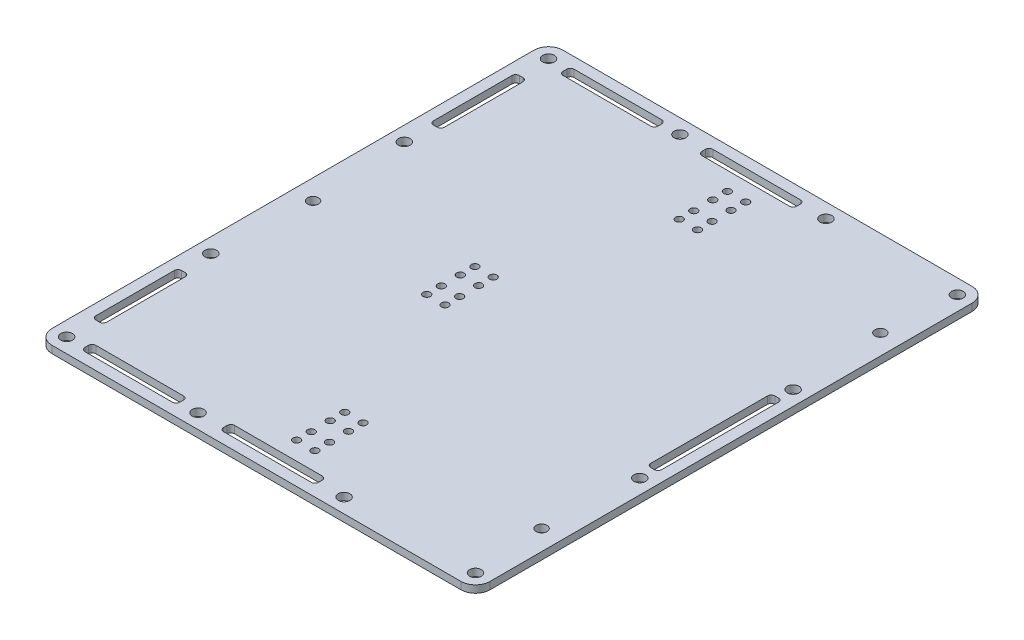
SolidWorks part; units mm, degrees
ref_plane "Front Plane" through (0, 0, 0) normal (0, 0, 1) x (1, 0, 0)
ref_plane "Top Plane" through (0, 0, 0) normal (0, 1, 0) x (1, 0, 0)
ref_plane "Right Plane" through (0, 0, 0) normal (1, 0, 0) x (0, 0, -1)
sketch "Sketch1" plane through (0, 0, 0) normal (0, 1, 0) x (1, 0, 0)
  line L1 (-60, -70) -> (60, -70)
  line L2 (-60, -70) -> (-60, 70)
  line L3 (-60, 70) -> (60, 70)
  line L4 (60, -70) -> (60, 70)
  line L5 (-60, -70) -> (60, 70) construction
  line L6 (-60, 70) -> (60, -70) construction
  point P0 (0, 0)
  dimension "D1" = 120
  dimension "D2" = 140
extrude "Boss-Extrude1" add sketch "Sketch1" along normal blind 4
sketch "Sketch9" plane through (0, 4, 0) normal (0, 1, 0) x (1, 0, 0)
  line L0 (-60, 70) -> (-60, -70) construction
  line L3 (60, -70) -> (60, 70) construction
  line L4 (60, 70) -> (-60, 70) construction
  line L5 (-60, -70) -> (60, -70) construction
  line L7 (-56, -70) -> (56, -70)
  line L8 (-60, -66) -> (-60, 66)
  line L9 (-56, 70) -> (56, 70)
  line L10 (60, -66) -> (60, 66)
  line L11 (-60, -70) -> (60, -70)
  line L12 (-60, -70) -> (-60, 70)
  line L13 (-60, 70) -> (60, 70)
  line L14 (60, -70) -> (60, 70)
  circle A0 centre (10, 66.8) radius 1.6
  circle A2 centre (-56.8, 25) radius 1.6
  circle A3 centre (-56.8, -25) radius 1.6
  circle A4 centre (10, -66.8) radius 1.6
  arc A6 (-60, -66) -> (-56, -70) centre (-56, -66) ccw
  arc A7 (60, -66) -> (56, -70) centre (56, -66) cw
  arc A8 (56, 70) -> (60, 66) centre (56, 66) cw
  arc A9 (-56, 70) -> (-60, 66) centre (-56, 66) ccw
  point P32 (-60, -70)
  point P37 (60, 70)
  line M37 (60, -70) -> (60, 70)
  line M38 (60, 70) -> (-60, 70)
  line M39 (-60, 70) -> (-60, -70)
  line M40 (-60, -70) -> (60, -70)
  dimension "D3" = 3.2
  dimension "D6" = 3.2
  dimension "D8" = 3.2
  dimension "D15" = 3.2
  dimension "D19" = 4
  dimension "D1" = 3.2
  dimension "D2" = 45
  dimension "D4" = 45
  dimension "D5" = 3.2
  dimension "D7" = 50
  dimension "D9" = 3.2
  dimension "D13" = 50
  dimension "D14" = 3.2
sketch "Sketch15" plane through (0, 4, 0) normal (0, 1, 0) x (1, 0, 0)
  line L0 (60, 70) -> (-60, 70) construction
  line L1 (-60, 70) -> (-60, -70) construction
  line L2 (-60, -70) -> (60, -70) construction
  line L3 (60, -70) -> (60, 70) construction
  line L4 (-60, -70) -> (60, -70) construction
  line L5 (-60, 70) -> (-60, -70) construction
  line L6 (60, 70) -> (-60, 70) construction
  line L7 (-60, 70) -> (-60, -70) construction
  line L8 (60, -70) -> (60, 70) construction
  line L9 (60, -70) -> (60, 70) construction
  circle A0 centre (-56, 66) radius 1.6
  circle A1 centre (-56, -66) radius 1.6
  circle A2 centre (56, -66) radius 1.6
  circle A3 centre (56, 66) radius 1.6
  circle A6 centre (-56, -26.5) radius 1.6
  circle A7 centre (-56, 26.5) radius 1.6
  circle A10 centre (20, 66) radius 1.6
  circle A11 centre (-20, 66) radius 1.6
  circle A12 centre (-20, -66) radius 1.6
  circle A13 centre (20, -66) radius 1.6
  circle A14 centre (56, -21) radius 1.6
  circle A15 centre (56, 21) radius 1.6
  dimension "D1" = 3.2
  dimension "D4" = 3.2
  dimension "D9" = 3.2
  dimension "D12" = 3.2
  dimension "D13" = 4
  dimension "D20" = 3.2
  dimension "D21" = 3.2
  dimension "D25" = 3.2
  dimension "D28" = 3.2
  dimension "D29" = 3.2
  dimension "D26" = 3.2
  dimension "D33" = 3.2
  dimension "D37" = 3.2
  dimension "D2" = 4
  dimension "D3" = 4
  dimension "D5" = 4
  dimension "D6" = 4
  dimension "D7" = 4
  dimension "D8" = 4
  dimension "D10" = 4
  dimension "D11" = 4
  dimension "D19" = 43.5
  dimension "D22" = 4
  dimension "D23" = 43.5
  dimension "D24" = 4
  dimension "D27" = 40
  dimension "D30" = 40
  dimension "D31" = 40
  dimension "D32" = 40
  dimension "D34" = 4
  dimension "D35" = 49
  dimension "D36" = 4
  dimension "D38" = 49
sketch "Sketch20" plane through (0, 4, 0) normal (0, 1, 0) x (1, 0, 0)
  line L0 (-52.5, -54.1) -> (-52.5, -57.1)
  line L1 (-52.5, -57.1) -> (-32.5, -57.1)
  line L2 (-32.5, -54.1) -> (-32.5, -57.1)
  line L3 (-52.5, -54.1) -> (-32.5, -54.1)
  line L4 (-60, -70) -> (60, -70) construction
  line L5 (-60, 70) -> (-60, -70) construction
  line L6 (-60, 70) -> (-60, -70) construction
  line L7 (0, 0) -> (-60, 0) construction
  line L8 (-52.5, -34.1) -> (-32.5, -34.1)
  line L9 (-52.5, -34.1) -> (-52.5, -37.1)
  line L10 (-52.5, -37.1) -> (-32.5, -37.1)
  line L11 (-32.5, -34.1) -> (-32.5, -37.1)
  line L12 (60, -70) -> (60, 70) construction
  line L13 (32.5, -11.5) -> (52.5, -11.5)
  line L14 (32.5, -11.5) -> (32.5, -8.5)
  line L15 (32.5, -8.5) -> (52.5, -8.5)
  line L16 (52.5, -11.5) -> (52.5, -8.5)
  line L19 (32.5, 8.5) -> (52.5, 8.5)
  line L20 (52.5, 11.5) -> (52.5, 8.5)
  line L21 (32.5, 11.5) -> (52.5, 11.5)
  line L22 (32.5, 11.5) -> (32.5, 8.5)
  line L23 (-52.5, 54.1) -> (-32.5, 54.1)
  line L24 (-52.5, 54.1) -> (-52.5, 57.1)
  line L25 (-52.5, 57.1) -> (-32.5, 57.1)
  line L26 (-32.5, 54.1) -> (-32.5, 57.1)
  line L27 (-52.5, 37.1) -> (-32.5, 37.1)
  line L28 (-32.5, 34.1) -> (-32.5, 37.1)
  line L29 (-52.5, 34.1) -> (-32.5, 34.1)
  line L30 (-52.5, 34.1) -> (-52.5, 37.1)
  dimension "D1" = 3
  dimension "D2" = 12.9
  dimension "D3" = 27.5
  dimension "D4" = 7.5
  dimension "D5" = 32.9
  dimension "D6" = 3
  dimension "D7" = 8.5
  dimension "D8" = 3
  dimension "D9" = 7.5
  dimension "D10" = 27.5
  dimension "D11" = 7.5
  dimension "D12" = 27.5
extrude "Boss-Extrude5" add sketch "Sketch20" along normal blind 8
sketch "Sketch25" plane through (0, 0, 57.1) normal (0, 0, 1) x (1, 0, 0)
  line L0 (-60, 4) -> (-60, 0) construction
  line L1 (-60, 4) -> (60, 4) construction
  line L2 (60, 4) -> (60, 0) construction
  line L5 (-60, 4) -> (60, 4) construction
  line L6 (-52.5, 4) -> (-32.5, 4) construction
  circle A0 centre (-47.5, 8) radius 1.6
  circle A1 centre (-37.5, 8) radius 1.6
  circle A2 centre (37.5, 8) radius 1.6
  circle A3 centre (47.5, 8) radius 1.6
  dimension "D5" = 3.2
  dimension "D6" = 3.2
  dimension "D7" = 3.2
  dimension "D8" = 3.2
  dimension "D1" = 12.5
  dimension "D2" = 22.5
  dimension "D3" = 4
  dimension "D4" = 4
  dimension "D9" = 10
  dimension "D10" = 12.5
  dimension "D11" = 4
  dimension "D12" = 4
extrude "Cut-Extrude21" cut sketch "Sketch25" against normal through all
extrude "Cut-Extrude22" cut sketch "Sketch9" against normal blind 10 contours A6 M39 M40 | A7 M37 M40 | A8 M38 M37 | A9 M38 M39 region at (-59.1065, 4, 69.1065) region at (59.1065, 4, 69.1065) region at (-59.1065, 4, -69.1065) region at (59.1065, 4, -69.1065)
sketch "Sketch26" plane through (0, 0, 0) normal (0, -1, 0) x (1, 0, 0)
  line L0 (25, -31) -> (25, 31)
  line L1 (60, 66) -> (60, -66) construction
  line L2 (45, -31) -> (45, 31)
  line L3 (-5, 31) -> (-5, -31)
  line L12 (-30, 52) -> (-50, 52)
  line L13 (-30, 52) -> (-30, 25)
  line L14 (-30, 25) -> (-50, 25)
  line L15 (-50, 52) -> (-50, 25)
  line L19 (-56, 70) -> (56, 70) construction
  line L23 (-60, -66) -> (-60, 66) construction
  line L28 (-5, -31) -> (15, -31)
  line L29 (56, -70) -> (-56, -70) construction
  line L30 (-35, -25) -> (-15, -25)
  line L31 (-35, -25) -> (-35, -52)
  line L32 (-35, -52) -> (-15, -52)
  line L33 (-15, -25) -> (-15, -52)
  line L34 (25, 31) -> (45, 31)
  line L38 (25, -31) -> (45, -31)
  line L42 (-5, 31) -> (15, 31)
  line L44 (15, 31) -> (15, -31)
  dimension "D3" = 45
  dimension "D4" = 20
  dimension "D5" = 39
  dimension "D6" = 45
  dimension "D9" = 10
  dimension "D10" = 27
  dimension "D11" = 20
  dimension "D12" = 25
  dimension "D14" = 39
  dimension "D15" = 20
  dimension "D16" = 27
  dimension "D17" = 45
  dimension "D18" = 39
  dimension "D19" = 39
  dimension "D20" = 15
  dimension "D22" = 20
extrude "Cut-Extrude24" cut sketch "Sketch15" against normal through all
sketch "Sketch28" plane through (0, 0, 70) normal (0, 0, 1) x (1, 0, 0)
  line L0 (-60, 0) -> (-60, 4) construction
  line L1 (-60, 2) -> (60, 2)
  line L2 (-60, 2) -> (-60, 14)
  line L3 (-60, 14) -> (60, 14)
  line L4 (60, 2) -> (60, 14)
  dimension "D1" = 120
  dimension "D2" = 12
extrude "Cut-Extrude25" cut sketch "Sketch28" against normal through all
extrude "Boss-Extrude6" add sketch "Sketch26" along normal blind 8
sketch "Sketch29" plane through (0, 0, -31) normal (0, 0, -1) x (-1, 0, 0)
  line L0 (-10.1, -3.4) -> (-10.1, -4.4) construction
  line L35 (-7.9, -3.4) -> (-7.9, -4.4)
  line L36 (-40.1, -3.4) -> (-40.1, -4.4) construction
  line L37 (-37.9, -3.4) -> (-37.9, -4.4)
  line L38 (-42.3, -3.4) -> (-42.3, -4.4)
  line L39 (-15, -8) -> (-15, 0) construction
  line L40 (-25, 0) -> (-45, 0) construction
  line L41 (-29.9, -3.4) -> (-29.9, -4.4) construction
  line L42 (-27.7, -3.4) -> (-27.7, -4.4)
  line L43 (-32.1, -3.4) -> (-32.1, -4.4)
  line L44 (-25, -8) -> (-25, 0) construction
  line L45 (-56, 0) -> (56, 0) construction
  line L48 (-12.3, -3.4) -> (-12.3, -4.4)
  line L57 (5, -8) -> (5, 0) construction
  line L68 (0.1, -3.4) -> (0.1, -4.4) construction
  line L69 (2.3, -3.4) -> (2.3, -4.4)
  line L70 (-2.1, -3.4) -> (-2.1, -4.4)
  line L81 (-45, -8) -> (-45, 0) construction
  arc A0 (-37.9, -3.4) -> (-42.3, -3.4) centre (-40.1, -3.4) ccw
  arc A1 (-42.3, -4.4) -> (-37.9, -4.4) centre (-40.1, -4.4) ccw
  arc A2 (-27.7, -3.4) -> (-32.1, -3.4) centre (-29.9, -3.4) ccw
  arc A3 (-32.1, -4.4) -> (-27.7, -4.4) centre (-29.9, -4.4) ccw
  arc A16 (-7.9, -3.4) -> (-12.3, -3.4) centre (-10.1, -3.4) ccw
  arc A17 (-12.3, -4.4) -> (-7.9, -4.4) centre (-10.1, -4.4) ccw
  arc A20 (2.3, -3.4) -> (-2.1, -3.4) centre (0.1, -3.4) ccw
  arc A21 (-2.1, -4.4) -> (2.3, -4.4) centre (0.1, -4.4) ccw
  point P2 (-40.1, -3.9)
  point P13 (-29.9, -3.9)
  point P24 (-10.1, -3.9)
  point P38 (0.1, -3.9)
  point P59 (30.1, -3.9)
  dimension "D2" = 2.2
  dimension "D6" = 2.2
  dimension "D13" = 2.2
  dimension "D15" = 4.9
  dimension "D22" = 2.2
  dimension "D1" = 1
  dimension "D4" = 3.9
  dimension "D5" = 1
  dimension "D7" = 4.9
  dimension "D8" = 3.9
  dimension "D11" = 4.9
  dimension "D12" = 1
  dimension "D14" = 3.9
  dimension "D18" = 4.9
  dimension "D23" = 1
  dimension "D24" = 3.9
sketch "Sketch30" plane through (0, 2, 0) normal (0, 1, 0) x (1, 0, 0)
  line L0 (-56, 70) -> (56, 70) construction
  line L1 (5, 49.8) -> (5, 55) construction
  line L5 (22.7344, 0) -> (-37.2656, 0) construction
  line L6 (0, -49.8) -> (0, -50.8) construction
  line L7 (5, -49.8) -> (5, -50.8) construction
  line L8 (0, 49.8) -> (0, 55) construction
  line L9 (-11.75, 2.6) -> (-11.75, -2.6) construction
  line L10 (-16.75, 2.6) -> (-16.75, -2.6) construction
  line L11 (-56, -70) -> (56, -70) construction
  line L12 (5, -54) -> (5, -55) construction
  line L13 (0, -54) -> (0, -55) construction
  line L14 (5, -49.8) -> (5, -55) construction
  line L15 (0, -49.8) -> (0, -55) construction
  line L16 (60, 66) -> (60, -66) construction
  line L17 (-60, 66) -> (-60, -66) construction
  circle A24 centre (5, 59) radius 1
  circle A25 centre (5, 49.8) radius 1
  circle A29 centre (5, 45.8) radius 1
  circle A30 centre (5, 55) radius 1
  circle A31 centre (5, 45.8) radius 1
  circle A32 centre (5, 55) radius 1
  circle A33 centre (5, -49.8) radius 1
  circle A34 centre (5, -55) radius 1
  circle A35 centre (5, -45.8) radius 1
  circle A36 centre (5, -59) radius 1
  circle A43 centre (0, -49.8) radius 1
  circle A44 centre (0, -55) radius 1
  circle A45 centre (0, -45.8) radius 1
  circle A46 centre (0, -59) radius 1
  circle A47 centre (0, 59) radius 1
  circle A48 centre (0, 45.8) radius 1
  circle A49 centre (0, 55) radius 1
  circle A50 centre (0, 49.8) radius 1
  circle A51 centre (-11.75, 2.6) radius 1
  circle A52 centre (-11.75, -2.6) radius 1
  circle A53 centre (-11.75, 6.6) radius 1
  circle A54 centre (-11.75, -6.6) radius 1
  circle A55 centre (-16.75, 2.6) radius 1
  circle A56 centre (-16.75, -2.6) radius 1
  circle A57 centre (-16.75, 6.6) radius 1
  circle A58 centre (-16.75, -6.6) radius 1
  point P6 (-11.75, 0)
  point P12 (5, 52.4)
  point P69 (-16.75, 0)
  point P82 (5, -52.4)
  point P83 (0, -52.4)
  dimension "D1" = 2
  dimension "D8" = 4
  dimension "D10" = 4
  dimension "D12" = 4
  dimension "D14" = 2
  dimension "D16" = 2
  dimension "D18" = 4
  dimension "D20" = 4
  dimension "D27" = 4
  dimension "D28" = 2
  dimension "D2" = 2
  dimension "D5" = 11
  dimension "D9" = 11
  dimension "D11" = 2
  dimension "D13" = 2
  dimension "D15" = 2
  dimension "D17" = 2
  dimension "D31" = 2
  dimension "D32" = 2
  dimension "D33" = 2
  dimension "D6" = 17.6
  dimension "D7" = 4
  dimension "D19" = 5.2
  dimension "D26" = 5.2
  dimension "D29" = 4
  dimension "D30" = 5.2
  dimension "D34" = 5
  dimension "D36" = 17.6
  dimension "D37" = 17.6
  dimension "D39" = 55
  dimension "D44" = 70
  dimension "D45" = 70
  dimension "D46" = 43.25
sketch "Sketch31" plane through (0, 0, -52) normal (0, 0, -1) x (-1, 0, 0)
  line L0 (19.9, -4.4) -> (19.9, -3.4) construction
  line L1 (17.7, -4.4) -> (17.7, -3.4)
  line L2 (22.1, -4.4) -> (22.1, -3.4)
  line L3 (35, 0) -> (15, 0) construction
  line L4 (15, -8) -> (15, 0) construction
  line L5 (30.1, -4.4) -> (30.1, -3.4) construction
  line L6 (27.9, -4.4) -> (27.9, -3.4)
  line L7 (32.3, -4.4) -> (32.3, -3.4)
  line L8 (-56, 0) -> (56, 0) construction
  line L9 (35, -8) -> (35, 0) construction
  arc A0 (17.7, -4.4) -> (22.1, -4.4) centre (19.9, -4.4) ccw
  arc A1 (22.1, -3.4) -> (17.7, -3.4) centre (19.9, -3.4) ccw
  arc A2 (27.9, -4.4) -> (32.3, -4.4) centre (30.1, -4.4) ccw
  arc A3 (32.3, -3.4) -> (27.9, -3.4) centre (30.1, -3.4) ccw
  point P2 (19.9, -3.9)
  point P13 (30.1, -3.9)
  dimension "D3" = 2.2
  dimension "D6" = 2.2
  dimension "D1" = 1
  dimension "D2" = 3.9
  dimension "D4" = 4.9
  dimension "D5" = 1
  dimension "D7" = 3.9
  dimension "D8" = 4.9
extrude "Cut-Extrude32" cut sketch "Sketch31" against normal blind 30
sketch "Sketch32" plane through (0, 0, 52) normal (0, 0, 1) x (1, 0, 0)
  line L0 (-45.1, -4.4) -> (-45.1, -3.4) construction
  line L1 (-47.3, -4.4) -> (-47.3, -3.4)
  line L2 (-42.9, -4.4) -> (-42.9, -3.4)
  line L3 (-56, 0) -> (56, 0) construction
  line L4 (-50, -8) -> (-50, 0) construction
  line L5 (-34.9, -4.4) -> (-34.9, -3.4) construction
  line L6 (-37.1, -4.4) -> (-37.1, -3.4)
  line L7 (-32.7, -4.4) -> (-32.7, -3.4)
  line L8 (-30, -8) -> (-30, 0) construction
  arc A0 (-47.3, -4.4) -> (-42.9, -4.4) centre (-45.1, -4.4) ccw
  arc A1 (-42.9, -3.4) -> (-47.3, -3.4) centre (-45.1, -3.4) ccw
  arc A2 (-37.1, -4.4) -> (-32.7, -4.4) centre (-34.9, -4.4) ccw
  arc A3 (-32.7, -3.4) -> (-37.1, -3.4) centre (-34.9, -3.4) ccw
  point P2 (-45.1, -3.9)
  point P13 (-34.9, -3.9)
  dimension "D2" = 2.2
  dimension "D6" = 2.2
  dimension "D1" = 1
  dimension "D3" = 3.9
  dimension "D4" = 4.9
  dimension "D5" = 1
  dimension "D7" = 3.9
  dimension "D8" = 4.9
extrude "Cut-Extrude33" cut sketch "Sketch32" against normal blind 30
extrude "Cut-Extrude34" cut sketch "Sketch30" against normal through all contours A24 | A47 | A30 | A49 | A50 | A25 | A29 | A48 | A57 | A53 | A51 | A55 | A56 | A52 | A35 | A43 | A33 | A34 | A46 | A36 | A54 | A58 | A45 | A44 | A58 region at (5, 2, -59) region at (5, 2, -49.8) region at (5, 2, -45.8) region at (5, 2, -55) region at (5, 2, 49.8) region at (5, 2, 55) region at (5, 2, 45.8) region at (5, 2, 59) region at (0, 2, 49.8) region at (0, 2, 59) region at (0, 2, -59) region at (0, 2, -45.8) region at (0, 2, -55) region at (0, 2, -49.8) region at (-11.75, 2, -2.6) region at (-11.75, 2, 2.6) region at (-11.75, 2, -6.6) region at (-11.75, 2, 6.6) region at (-16.75, 2, -2.6) region at (-16.75, 2, 2.6) region at (-16.75, 2, -6.6) region at (-16.75, 2, 6.6)
extrude "Cut-Extrude35" cut sketch "Sketch29" against normal through all
sketch "Sketch33" plane through (0, -8, 0) normal (0, -1, 0) x (1, 0, 0)
  line L8 (-15, -52) -> (-15, -25) construction
  line L9 (-35, -52) -> (-15, -52)
  line L10 (-35, -52) -> (-35, -41.5)
  line L11 (-35, -41.5) -> (-15, -41.5)
  line L12 (-15, -52) -> (-15, -41.5)
  line L13 (-15, -25) -> (-35, -25) construction
  line L14 (25, 31) -> (25, -31) construction
  line L15 (25, 14.5) -> (45, 14.5)
  line L16 (25, 14.5) -> (25, -14.5)
  line L17 (25, -14.5) -> (45, -14.5)
  line L18 (45, 14.5) -> (45, -14.5)
  line L19 (45, -31) -> (45, 31) construction
  line L20 (45, 31) -> (25, 31) construction
  line L21 (25, -31) -> (45, -31) construction
  dimension "D3" = 16.5
  dimension "D4" = 16.5
  dimension "D5" = 16.5
extrude "Cut-Extrude36" cut sketch "Sketch33" against normal blind 8
sketch "Sketch34" plane through (0, 2, 0) normal (0, 1, 0) x (1, 0, 0)
  line L0 (-60, 66) -> (-60, -66) construction
  line L5 (-50, -64) -> (-26, -64)
  line L6 (-51, -65) -> (-51, -66)
  line L7 (-50, -67) -> (-26, -67)
  line L8 (-25, -65) -> (-25, -66)
  line L9 (-56, -34.5) -> (-55, -34.5)
  line L10 (-57, -35.5) -> (-57, -57)
  line L11 (-56, -58) -> (-55, -58)
  line L12 (-54, -35.5) -> (-54, -57)
  line L13 (-12, -64) -> (12, -64)
  line L14 (-13, -65) -> (-13, -66)
  line L15 (-12, -67) -> (12, -67)
  line L16 (13, -65) -> (13, -66)
  line L17 (-56, -70) -> (56, -70) construction
  line L18 (60, 66) -> (60, -66) construction
  line L19 (55, 17) -> (56, 17)
  line L20 (54, 16) -> (54, -16)
  line L21 (55, -17) -> (56, -17)
  line L22 (57, 16) -> (57, -16)
  line L23 (-56, 70) -> (56, 70) construction
  line L24 (0, 0) -> (-60, 0) construction
  arc A0 (56, -17) -> (57, -16) centre (56, -16) ccw
  arc A1 (54, -16) -> (55, -17) centre (55, -16) ccw
  arc A2 (56, 17) -> (57, 16) centre (56, 16) cw
  arc A3 (55, 17) -> (54, 16) centre (55, 16) ccw
  arc A4 (12, -64) -> (13, -65) centre (12, -65) cw
  arc A5 (12, -67) -> (13, -66) centre (12, -66) ccw
  arc A6 (-12, -64) -> (-13, -65) centre (-12, -65) ccw
  arc A7 (-13, -66) -> (-12, -67) centre (-12, -66) ccw
  arc A8 (-26, -64) -> (-25, -65) centre (-26, -65) cw
  arc A9 (-26, -67) -> (-25, -66) centre (-26, -66) ccw
  arc A10 (-51, -66) -> (-50, -67) centre (-50, -66) ccw
  arc A11 (-50, -64) -> (-51, -65) centre (-50, -65) ccw
  arc A12 (-55, -58) -> (-54, -57) centre (-55, -57) ccw
  arc A13 (-57, -57) -> (-56, -58) centre (-56, -57) ccw
  arc A14 (-55, -34.5) -> (-54, -35.5) centre (-55, -35.5) cw
  arc A15 (-56, -34.5) -> (-57, -35.5) centre (-56, -35.5) ccw
  point P26 (57, -17)
  point P29 (54, -17)
  point P32 (57, 17)
  point P37 (13, -64)
  point P40 (13, -67)
  point P45 (-13, -67)
  point P48 (-25, -64)
  point P51 (-25, -67)
  point P54 (-51, -67)
  point P59 (-54, -58)
  point P62 (-57, -58)
  point P67 (-57, -34.5)
  dimension "D17" = 1
  dimension "D1" = 23.5
  dimension "D2" = 3
  dimension "D3" = 3
  dimension "D4" = 12
  dimension "D5" = 3
  dimension "D6" = 3
  dimension "D7" = 26
  dimension "D8" = 9
  dimension "D9" = 3
  dimension "D10" = 3
  dimension "D11" = 26
  dimension "D12" = 47
  dimension "D13" = 34
  dimension "D14" = 3
  dimension "D15" = 3
  dimension "D16" = 53
extrude "Cut-Extrude37" cut sketch "Sketch34" against normal through all
mirror "Mirror1" about plane through (0, 0, 0) normal (0, 0, 1) of "Cut-Extrude37"
fillet "Fillet1" radius 0.5 24 edges at (5, 0, -60) (0, 0, -60) (0, 0, -56) (5, 0, -56) (5, 0, -50.8) (0, 0, -50.8) (0, 0, -46.8) (5, 0, -46.8) (-11.75, 0, -7.6) (-16.75, 0, -7.6) (-16.75, 0, -3.6) (-11.75, 0, -3.6) (-11.75, 0, 1.6) (-16.75, 0, 1.6) (-16.75, 0, 5.6) (-11.75, 0, 5.6) (0, 0, 44.8) (5, 0, 44.8) (5, 0, 48.8) (0, 0, 48.8) (5, 0, 54) (0, 0, 54) (5, 0, 58) (0, 0, 58)
sketch "Sketch35" plane through (0, 0, 0) normal (0, -1, 0) x (1, 0, 0)
  line L0 (56, -70) -> (-56, -70) construction
  line L1 (-56, 70) -> (56, 70) construction
  line L2 (-60, -66) -> (-60, 66) construction
  line L3 (60, 66) -> (60, -66) construction
  circle A0 centre (54.5, -46.4) radius 1.5
  circle A1 centre (-54.5, 0) radius 1.5
  circle A2 centre (54.5, 46.4) radius 1.5
  dimension "D1" = 3
  dimension "D2" = 3
  dimension "D6" = 3
  dimension "D3" = 23.6
  dimension "D4" = 23.6
  dimension "D5" = 5.5
  dimension "D7" = 70
  dimension "D8" = 5.5
  dimension "D9" = 5.5
extrude "Cut-Extrude38" cut sketch "Sketch35" against normal blind 10
